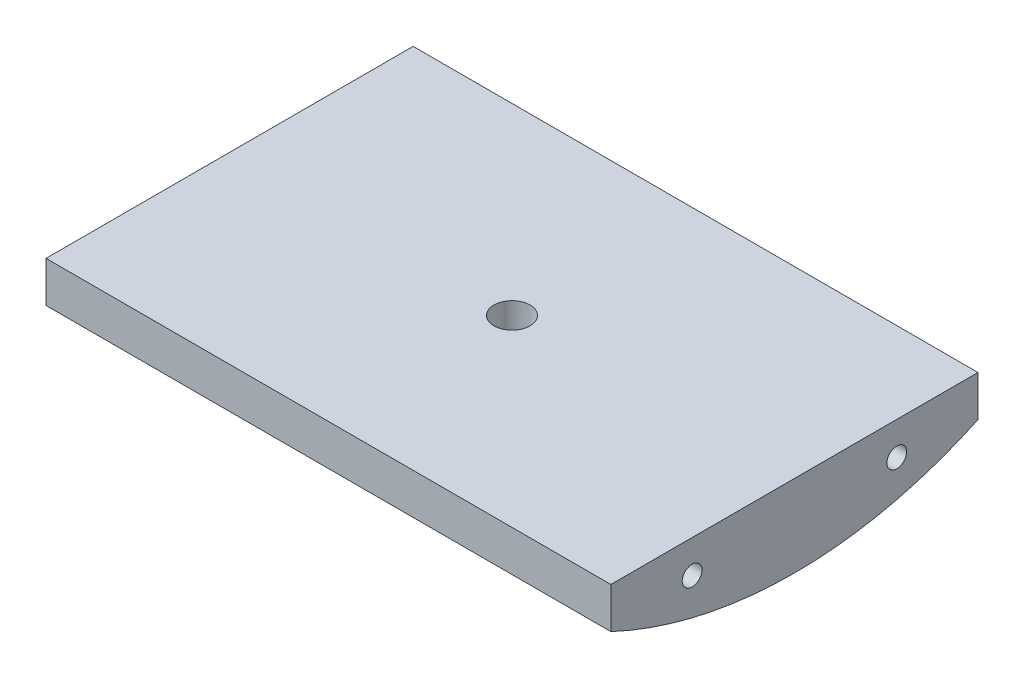
SolidWorks part; units mm, degrees
ref_plane "Front Plane" through (0, 0, 0) normal (0, 0, 1) x (1, 0, 0)
ref_plane "Top Plane" through (0, 0, 0) normal (0, 1, 0) x (1, 0, 0)
ref_plane "Right Plane" through (0, 0, 0) normal (1, 0, 0) x (0, 0, -1)
sketch "Sketch1" plane through (0, 0, 0) normal (1, 0, 0) x (0, 0, -1)
  line L0 (0, 0) -> (0, -90.5205) construction
  line L1 (-32.5, -61.79) -> (32.5, -61.79)
  line L2 (-32.5, -61.79) -> (-32.5, -69.0211)
  line L3 (0, 0) -> (18.1173, -67.6148) construction
  line L4 (32.5, -61.79) -> (32.5, -69.0211)
  line L5 (-18.1173, -67.6148) -> (0, 0) construction
  arc A0 (-32.5, -69.0211) -> (32.5, -69.0211) centre (0, 0) ccw construction
  arc A1 (-32.5, -69.0211) -> (32.5, -69.0211) centre (0, 0) ccw
  circle A2 centre (0, 0) radius 76.29 construction
  circle A3 centre (18.1173, -67.6148) radius 1.75
  circle A4 centre (-18.1173, -67.6148) radius 1.75
  point P7 (0, -76.29)
  dimension "D1" = 152.58
  dimension "D5" = 3.5
  dimension "D2" = 14.5
  dimension "D3" = 65
  dimension "D4" = 30
  dimension "D6" = 70
extrude "Boss-Extrude1" add sketch "Sketch1" along normal blind 100
sketch "Sketch2" plane through (0, -61.79, 0) normal (0, 1, 0) x (1, 0, 0)
  line L0 (0, 32.5) -> (100, -32.5) construction
  line L1 (0, -32.5) -> (100, 32.5) construction
  circle A0 centre (50, 0) radius 3.2
  dimension "D1" = 6.4
extrude "Cut-Extrude1" cut sketch "Sketch2" against normal through all
